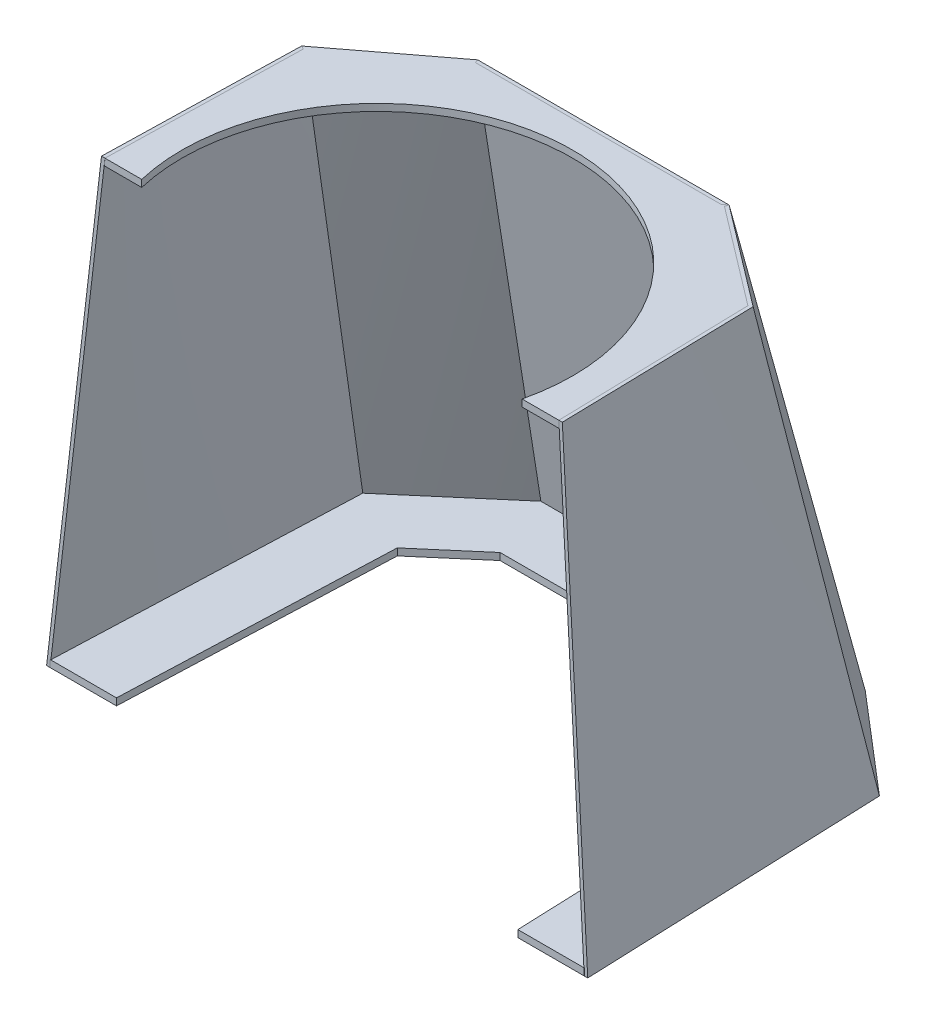
SolidWorks part; units mm, degrees
ref_plane "Front Plane" through (0, 0, 0) normal (0, 0, 1) x (1, 0, 0)
ref_plane "Top Plane" through (0, 0, 0) normal (0, 1, 0) x (1, 0, 0)
ref_plane "Right Plane" through (0, 0, 0) normal (1, 0, 0) x (0, 0, -1)
sketch "Sketch1" plane through (0, 0, 0) normal (0, 1, 0) x (1, 0, 0)
  line L0 (-387.5, -345.2977) -> (-370.5478, 89.3719)
  line L1 (-370.5478, 89.3719) -> (-230, 209.6687)
  line L2 (-230, 209.6687) -> (230, 209.6687)
  line L3 (230, 209.6687) -> (370.5478, 89.3719)
  line L4 (370.5478, 89.3719) -> (387.5, -345.2977)
  line L5 (-387.5, -345.2977) -> (0, 209.6687) construction
  line L6 (-382.4962, -345.2977) -> (-365.6367, 86.9939)
  line L7 (-365.6367, 86.9939) -> (-228.1524, 204.6687)
  line L8 (-228.1524, 204.6687) -> (228.1524, 204.6687)
  line L9 (228.1524, 204.6687) -> (365.6367, 86.9939)
  line L10 (365.6367, 86.9939) -> (382.4962, -345.2977)
  line L11 (-387.5, -345.2977) -> (-287.424, -345.2977)
  line L12 (-272.3266, 41.8129) -> (-193.0479, 109.6687)
  line L13 (-193.0479, 109.6687) -> (193.0479, 109.6687)
  line L14 (193.0479, 109.6687) -> (272.3266, 41.8129)
  line L15 (272.3266, 41.8129) -> (283.524, -245.2977)
  line L17 (-283.524, -245.2977) -> (-272.3266, 41.8129)
  line L18 (-283.524, -245.2977) -> (283.524, -245.2977) construction
  line L19 (-283.524, -245.2977) -> (-287.424, -345.2977)
  line L20 (283.524, -245.2977) -> (287.424, -345.2977)
  line L21 (287.424, -345.2977) -> (387.5, -345.2977)
  line L22 (-387.5, -345.2977) -> (387.5, -345.2977) construction
  line L23 (365.6367, 86.9939) -> (382.5038, -345.4926) construction
  line L24 (-382.5038, -345.4926) -> (-365.6367, 86.9939) construction
  point P6 (0, 209.6687)
  dimension "D1" = 460
  dimension "D2" = 185
  dimension "D3" = 435
  dimension "D4" = 5
  dimension "D6" = 775
  dimension "D5" = 100
ref_plane "Plane1" through (0, 650, 0) normal (0, 1, 0) x (1, 0, 0)
sketch "Sketch2" plane through (0, 650, 0) normal (0, 1, 0) x (1, 0, 0)
  line L0 (-330, -324.1758) -> (-323.3019, -44.2559)
  line L1 (-323.3019, -44.2559) -> (-180, 64.6687)
  line L2 (-180, 64.6687) -> (180, 64.6687)
  line L3 (180, 64.6687) -> (323.3019, -44.2559)
  line L4 (323.3019, -44.2559) -> (330, -324.1758)
  line L5 (-330, -324.1758) -> (0, 64.6687) construction
  line L6 (-324.9986, -324.1758) -> (-318.3609, -46.7807)
  line L7 (-318.3609, -46.7807) -> (-178.3154, 59.6687)
  line L8 (-178.3154, 59.6687) -> (178.3154, 59.6687)
  line L9 (178.3154, 59.6687) -> (318.3609, -46.7807)
  line L10 (318.3609, -46.7807) -> (324.9986, -324.1758)
  line L13 (330, -324.1758) -> (271.1088, -324.1758)
  line L14 (318.3609, -46.7807) -> (325.0014, -324.2954) construction
  line L16 (-271.1088, -324.1758) -> (-330, -324.1758)
  line L17 (-325.0014, -324.2954) -> (-318.3609, -46.7807) construction
  line L19 (-330, -324.1758) -> (-271.1088, -324.1758) construction
  line L20 (271.1088, -324.1758) -> (318.3609, -324.1758) construction
  line L22 (-330, -324.1758) -> (-271.1088, -324.1758)
  line L23 (271.1088, -324.1758) -> (330, -324.1758)
  arc A2 (272.3509, -324.1758) -> (-272.3509, -324.1758) centre (0, -259.1758) ccw
  point P28 (0, -324.1758)
  dimension "D8" = 560
  dimension "D1" = 360
  dimension "D2" = 180
  dimension "D3" = 280
  dimension "D4" = 510
  dimension "D5" = 660
  dimension "D6" = 145
  dimension "D7" = 5
loft "Loft1" add section "Sketch1" section "Sketch2" connector at (-365.6367, 0, -86.9939) connector at (-318.3609, 650, 46.7807)
extrude "Boss-Extrude1" add sketch "Sketch1<51>" along normal blind 10 contours L20 L21 L10 L9 L8 L7 L6 L11 L19 L17 L12 L13 L14 L15 region at (-364.652, 0, 129.5191)
sketch "Sketch1<51>" plane through (0, 0, 0) normal (0, 1, 0) x (1, 0, 0) same geometry as "Sketch1"
extrude "Boss-Extrude2" add sketch "Sketch2<31>" against normal blind 10 separate body contours L13 L10 L9 L8 L7 L6 L16 | L16 L6 L7 L8 L9 L10 L13 L4 L3 L2 L1 L0 region at (-325.8851, 650, 184.2342) region at (-314.1332, 650, 185.6588)
sketch "Sketch2<31>" plane through (0, 650, 0) normal (0, 1, 0) x (1, 0, 0) same geometry as "Sketch2"
